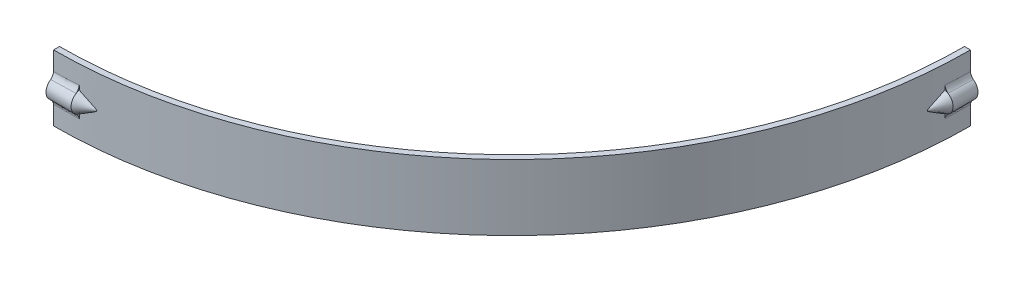
SolidWorks part; units mm, degrees
ref_plane "Front Plane" through (0, 0, 0) normal (0, 0, 1) x (1, 0, 0)
ref_plane "Top Plane" through (0, 0, 0) normal (0, 1, 0) x (1, 0, 0)
ref_plane "Right Plane" through (0, 0, 0) normal (1, 0, 0) x (0, 0, -1)
sketch "Sketch1" plane through (0, 0, 0) normal (0, 0, 1) x (1, 0, 0)
  line L0 (0, 3.3639) -> (0, -36.2756) construction
  line L1 (176.7332, 12.7) -> (174.4472, 12.7)
  line L2 (176.7332, 12.7) -> (176.7332, -12.7)
  line L3 (176.7332, -12.7) -> (174.4472, -12.7)
  line L4 (174.4472, 12.7) -> (174.4472, -12.7)
  line L5 (176.7332, 12.7) -> (174.4472, -12.7) construction
  line L6 (176.7332, -12.7) -> (174.4472, 12.7) construction
  point P0 (175.5902, 0)
  dimension "D1" = 25.4
  dimension "D2" = 2.286
  dimension "D3" = 175.5902
revolve "Revolve1" add sketch "Sketch1" angle 90 about L0
sketch "Sketch4" plane through (0, 0, 0) normal (-1, 0, 0) x (0, 0, 1)
  line L1 (176.7332, 12.7) -> (174.4472, 12.7) construction
  circle A0 centre (175.5902, 0) radius 4.064
  point P5 (175.5902, 12.7)
  dimension "D2" = 8.128
extrude "Boss-Extrude1" add sketch "Sketch4" against normal blind 9.652
sketch "Sketch6" plane through (9.652, 0, 0) normal (1, 0, 0) x (0, 0, -1)
  circle A0 centre (-175.5902, 0) radius 3.175
  circle A2 centre (-175.5902, 0) radius 4.064 construction
  dimension "D1" = 6.35
fillet "Fillet6" radius 2.54 2 edges at (8.128, 3.95, 176.5462) (1.5261, -3.9019, 176.7266) conic radius 5.08
fillet "Fillet8" radius 2.54 2 edges at (8.128, -3.8394, 174.2577) (1.526, 3.898, 174.4405) conic radius 5.08
sketch "Sketch7" plane through (0, 0, 0) normal (0, 0, -1) x (-1, 0, 0)
  line L1 (-176.7332, 12.7) -> (-174.4472, 12.7) construction
  circle A0 centre (-175.5902, 0) radius 4.064
  point P7 (-175.5902, 12.7)
  dimension "D1" = 8.128
extrude "Boss-Extrude2" add sketch "Sketch7" against normal blind 9.6012
sketch "Sketch8" plane through (0, 0, 9.6012) normal (0, 0, 1) x (1, 0, 0)
  circle A0 centre (175.5902, 0) radius 3.175
  circle A1 centre (175.5902, 0) radius 4.064 construction
  dimension "D1" = 6.35
fillet "Fillet11" radius 2.54 4 edges at (174.441, -3.8981, 1.4752) (174.2577, 3.8394, 8.128) (176.5462, -3.95, 8.128) (176.727, 3.9018, 1.4752) conic radius 5.08
sketch "Sketch9" plane through (0, 0, 0) normal (-1, 0, 0) x (0, 0, 1)
  circle A0 centre (175.5902, 0) radius 3.3655
  dimension "D1" = 6.731
extrude "Cut-Extrude1" cut sketch "Sketch9" against normal blind 9.525
sketch "Sketch10" plane through (0, 0, 0) normal (0, 0, -1) x (-1, 0, 0)
  circle A0 centre (-175.5902, 0) radius 3.3655
  dimension "D1" = 6.731
extrude "Cut-Extrude2" cut sketch "Sketch10" against normal blind 9.525
sketch "Sketch11" plane through (0, 0, 0) normal (0, 1, 0) x (1, 0, 0)
  line L0 (9.652, -171.5262) -> (9.652, -175.4632)
  line L1 (9.652, -179.6542) -> (16.4711, -175.7172)
  line L2 (16.4711, -175.4632) -> (9.652, -171.5262)
  line L3 (9.652, -175.5902) -> (13.6215, -175.5902) construction
  line L4 (9.652, -175.4632) -> (16.4711, -175.4632)
  line L5 (16.4711, -175.7172) -> (9.652, -175.7172)
  line L6 (9.652, -175.7172) -> (9.652, -179.6542)
  line L7 (9.652, -178.7652) -> (9.652, -172.4152) construction
  dimension "D1" = 60
  dimension "D2" = 60
  dimension "D3" = 0.254
revolve "Revolve7" add sketch "Sketch11" angle 180 about L3
sketch "Sketch12" plane through (0, 0, 0) normal (0, 1, 0) x (1, 0, 0)
  line L0 (171.5262, -9.6012) -> (175.4632, -16.4203)
  line L1 (175.7172, -16.4203) -> (179.6542, -9.6012)
  line L2 (177.6983, -9.6012) -> (179.6542, -9.6012) construction
  line L3 (179.6542, -9.6012) -> (175.7172, -9.6012)
  line L4 (175.7172, -9.6012) -> (175.7172, -16.4203)
  line L6 (175.4632, -16.4203) -> (175.4632, -9.6012)
  line L7 (175.5902, -9.9069) -> (175.5902, -14.0613) construction
  line L8 (175.4632, -9.6012) -> (171.5262, -9.6012)
  dimension "D1" = 60
  dimension "D2" = 60
  dimension "D3" = 0.254
  dimension "D4" = 0.127
revolve "Revolve8" add sketch "Sketch12" angle 203 about L7
